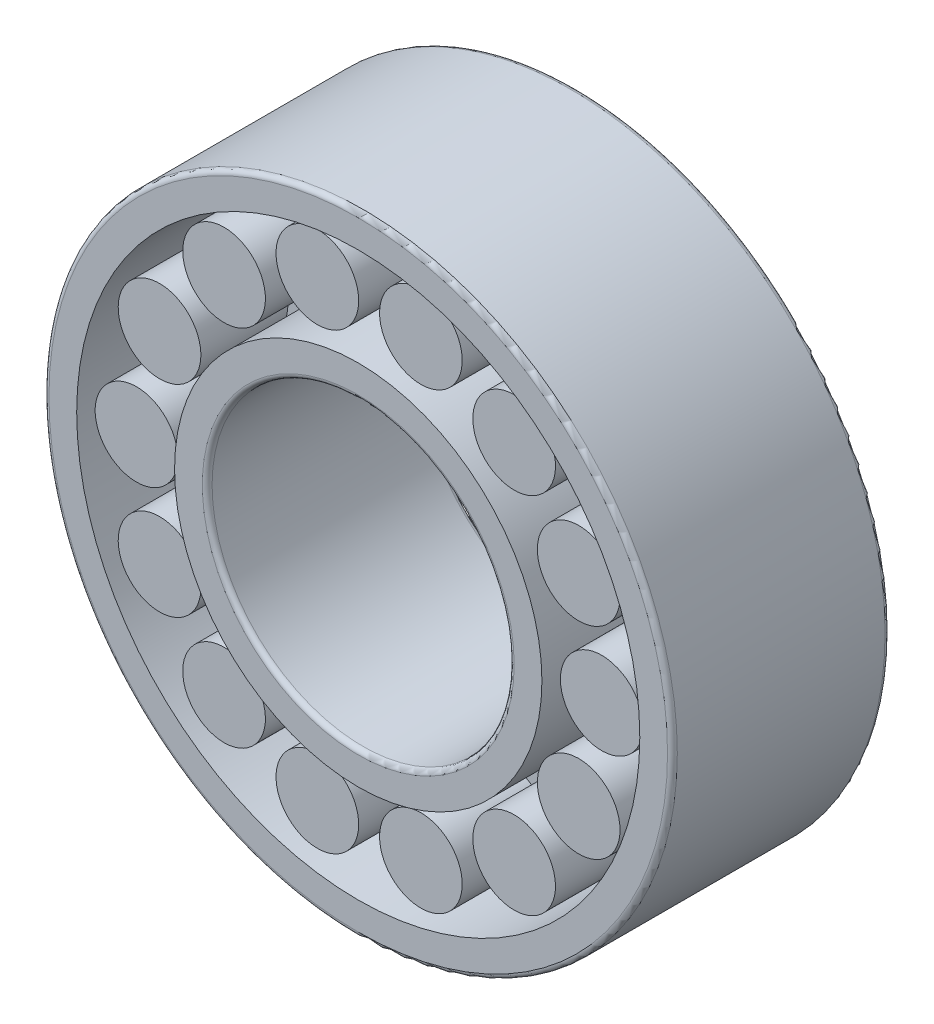
SolidWorks part; units mm, degrees
ref_plane "Front Plane" through (0, 0, 0) normal (0, 0, 1) x (1, 0, 0)
ref_plane "Top Plane" through (0, 0, 0) normal (0, 1, 0) x (1, 0, 0)
ref_plane "Right Plane" through (0, 0, 0) normal (1, 0, 0) x (0, 0, -1)
sketch "S" plane through (0, 0, 0) normal (0, 0, 1) x (1, 0, 0)
  line L0 (-9, 0) -> (9, 0) construction
  circle A0 centre (0, 0) radius 12.5 construction
  circle A1 centre (0, 0) radius 26 construction
  circle A2 centre (0, 0) radius 15.2 construction
  circle A3 centre (0, 0) radius 23.3 construction
  dimension "ID" = 25
  dimension "OD" = 52
  dimension "IDa" = 30.4
  dimension "ODa" = 46.6
  dimension "B" = 18
ref_axis "Z" through (0, 0, -9.9) along (0, 0, 1)
sketch "InnerS" plane through (0, 0, 0) normal (0, 1, 0) x (1, 0, 0)
  line L0 (12.5, -9) -> (15.2, -9)
  line L1 (15.2, -9) -> (15.2, 9)
  line L2 (15.2, 9) -> (12.5, 9)
  line L3 (12.5, 9) -> (12.5, -9)
  line L4 (0, -14.5) -> (0, 14.5) construction
  dimension "r1" = 12.5
  dimension "r2" = 15.2
  dimension "z1" = 9
  dimension "z2" = 9
revolve "InnerRing" add sketch "InnerS" angle 360 about L4
sketch "OuterS" plane through (0, 0, 0) normal (0, 1, 0) x (1, 0, 0)
  line L0 (23.3, -9) -> (26, -9)
  line L1 (26, -9) -> (26, 9)
  line L2 (26, 9) -> (23.3, 9)
  line L3 (23.3, 9) -> (23.3, -9)
  line L4 (0, -14.5) -> (0, 14.5) construction
  dimension "z1" = 9
  dimension "z2" = 9
  dimension "r1" = 23.3
  dimension "r2" = 26
revolve "OuterRing" add sketch "OuterS" angle 360 about L4
sketch "Roller1S" plane through (0, 0, 0) normal (0, 1, 0) x (1, 0, 0)
  line L0 (19.25, 0.9) -> (22.67, 0.9)
  line L1 (22.67, 0.9) -> (22.67, 8.1)
  line L2 (22.67, 8.1) -> (19.25, 8.1)
  line L3 (19.25, 8.1) -> (19.25, 0.9)
  dimension "r1" = 19.25
  dimension "r2" = 22.67
  dimension "z2" = 8.1
revolve "Roller1" add sketch "Roller1S" angle 360 about L3
pattern_circular "Roller1sPattern" count 14 over 360 about axis through (0, 0, -9.9) along (0, 0, 1) of bodies 103
sketch "Roller2S" plane through (0, 0, 0) normal (0, 1, 0) x (1, 0, 0)
  line L0 (19.25, -8.1) -> (22.67, -8.1)
  line L1 (22.67, -8.1) -> (22.67, -0.9)
  line L2 (22.67, -0.9) -> (19.25, -0.9)
  line L3 (19.25, -0.9) -> (19.25, -8.1)
  dimension "r1" = 19.25
  dimension "r2" = 22.67
  dimension "z1" = 8.1
revolve "Roller2" add sketch "Roller2S" angle 360 about L3
pattern_circular "Roller2sPattern" count 14 over 360 about axis through (0, 0, -9.9) along (0, 0, 1) of bodies 117
fillet "F1" radius 0.405 2 edges at (26, 0, -9) (26, 0, 9)
fillet "F2" radius 0.405 2 edges at (12.5, 0, -9) (12.5, 0, 9)
equation "\"r1@InnerS\" = abs(0.5*\"ID@S\")"
equation "\"r2@InnerS\" = abs(0.5*\"IDa@S\")"
equation "\"z1@InnerS\" = abs(-0.5*\"B@S\")"
equation "\"z2@InnerS\" = abs(0.5*\"B@S\")"
equation "\"r1@OuterS\" = abs(0.5*\"ODa@S\")"
equation "\"r2@OuterS\" = abs(0.5*\"OD@S\")"
equation "\"z1@OuterS\" = abs(-0.5*\"B@S\")"
equation "\"z2@OuterS\" = abs(0.5*\"B@S\")"
equation "\"r1@Roller1S\" = abs(0.25*\"IDa@S\"+0.25*\"ODa@S\")"
equation "\"r2@Roller1S\" = abs(0.25*\"IDa@S\"+0.25*\"ODa@S\"+0.19*\"B@S\")"
equation "\"z1@Roller1S\" = abs(0.05*\"B@S\")"
equation "\"z2@Roller1S\" = abs(0.45*\"B@S\")"
equation "\"N@Roller1sPattern\" = int(5.027*(0.25*\"IDa@S\"+0.25*\"ODa@S\")/(0.38*\"B@S\"))"
equation "\"r1@Roller2S\" = abs(0.25*\"IDa@S\"+0.25*\"ODa@S\")"
equation "\"r2@Roller2S\" = abs(0.25*\"IDa@S\"+0.25*\"ODa@S\"+0.19*\"B@S\")"
equation "\"z1@Roller2S\" = abs(-0.45*\"B@S\")"
equation "\"z2@Roller2S\" = abs(-0.05*\"B@S\")"
equation "\"N@Roller2sPattern\" = int(5.027*(0.25*\"IDa@S\"+0.25*\"ODa@S\")/(0.38*\"B@S\"))"
equation "\"r_min@F2\" = \"r_min@F1\""
